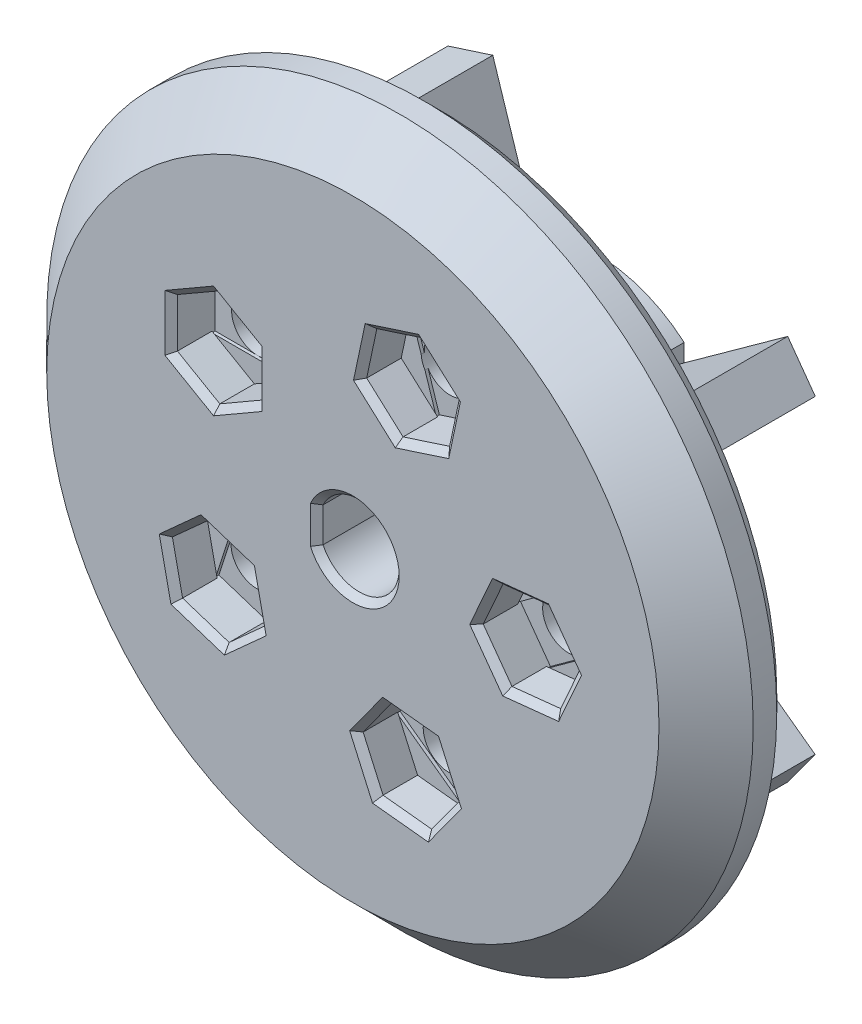
SolidWorks part; units mm, degrees
ref_plane "Front Plane" through (0, 0, 0) normal (0, 0, 1) x (1, 0, 0)
ref_plane "Top Plane" through (0, 0, 0) normal (0, 1, 0) x (1, 0, 0)
ref_plane "Right Plane" through (0, 0, 0) normal (1, 0, 0) x (0, 0, -1)
sketch "Sketch1" plane through (0, 0, 0) normal (0, 0, 1) x (1, 0, 0)
  circle A0 centre (0, 0) radius 22.5
  arc A1 (-1.7397, -1.8644) -> (-1.7397, 1.8644) centre (0, 0) ccw
  arc A2 (-1.7397, 1.8644) -> (-1.7397, -1.8644) centre (0, 0) ccw
  dimension "D1" = 45
  dimension "D2" = 5.1
extrude "Boss-Extrude1" add sketch "Sketch1" along normal blind 5.5
sketch "Sketch2" plane through (0, 0, 0) normal (0, 0, -1) x (-1, 0, 0)
  line L0 (0, 0) -> (-18.85, 0) construction
  line L1 (0, 0) -> (-5.825, 17.9274) construction
  line L2 (0, 0) -> (15.25, 11.0798) construction
  line L3 (0, 0) -> (15.25, -11.0798) construction
  line L4 (0, 0) -> (-5.825, -17.9274) construction
  line L5 (-22.5, 0) -> (-20.375, 0) construction
  circle A0 centre (-18.85, 0) radius 5.5 construction
  circle A3 centre (-18.85, 0) radius 1.525
  circle A4 centre (-5.825, 17.9274) radius 5.5 construction
  circle A5 centre (-5.825, 17.9274) radius 1.525
  circle A6 centre (15.25, 11.0798) radius 5.5 construction
  circle A7 centre (15.25, 11.0798) radius 1.525
  circle A8 centre (15.25, -11.0798) radius 5.5 construction
  circle A9 centre (15.25, -11.0798) radius 1.525
  circle A10 centre (-5.825, -17.9274) radius 5.5 construction
  circle A11 centre (-5.825, -17.9274) radius 1.525
  circle A13 centre (0, 0) radius 22.5 construction
  point P24 (0, 0)
  dimension "D1" = 11
  dimension "D2" = 3.65
  dimension "D3" = 3.05
  dimension "D4" = 5
extrude "Cut-Extrude1" cut sketch "Sketch2" against normal blind 3.5
sketch "Sketch3" plane through (0, 0, 0) normal (0, 0, -1) x (-1, 0, 0)
  line L3 (-10.9375, 0) -> (-8.55, 0) construction
  line L4 (-10.9375, 0) -> (-13.325, 0) construction
  circle A0 centre (0, 0) radius 8.55 construction
  circle A1 centre (0, 0) radius 2.55 construction
  circle A2 centre (0, 0) radius 2.55
  circle A3 centre (-18.85, 0) radius 5.525 construction
  circle A4 centre (-18.85, 0) radius 1.525 construction
  circle A6 centre (-10.9375, 0) radius 1.65
  circle A7 centre (-3.3953, 10.4497) radius 1.65
  circle A8 centre (8.8736, 6.5058) radius 1.65
  circle A9 centre (8.9141, -6.3813) radius 1.65
  circle A10 centre (-3.3299, -10.4022) radius 1.65
  point P27 (0.025, 0.0344)
  dimension "D1" = 6
  dimension "D2" = 4
  dimension "D3" = 3.3
extrude "Cut-Extrude2" cut sketch "Sketch3" against normal through all both and the other way through all
sketch "Sketch4" plane through (0, 0, 0) normal (0, 0, -1) x (-1, 0, 0)
  circle A0 centre (0, 0) radius 8.55
  circle A2 centre (0, 0) radius 2.55 construction
  circle A3 centre (0, 0) radius 2.55
  dimension "D1" = 6
extrude "Boss-Extrude2" add sketch "Sketch4" along normal blind 10
ref_plane "Plane1" through (-8.55, 0, 0) normal (-1, 0, 0) x (0, 0, 1)
sketch "Sketch8" plane through (0, 0, -10) normal (0, 0, -1) x (-1, 0, 0)
  line L0 (2.3, 1.1011) -> (2.3, -1.1011)
  line L1 (2.3, 0) -> (-2.55, 0) construction
  circle A0 centre (0, 0) radius 2.55 construction
  arc A1 (2.3, -1.1011) -> (2.3, 1.1011) centre (0, 0) ccw
  arc A2 (-2.55, 0) -> (2.3, -1.1011) centre (0, 0) ccw construction
  arc A3 (2.3, 1.1011) -> (-2.55, 0) centre (0, 0) ccw construction
  dimension "D1" = 4.85
extrude "Boss-Extrude3" add sketch "Sketch8" against normal up to surface (15.5 mm away) up to face at (1.6799, -10.4022, 5.5)
sketch "Sketch5" plane through (-8.55, 0, 0) normal (-1, 0, 0) x (0, 0, 1)
  line L0 (0, 0) -> (-10, 0) construction
  line L1 (-10, 8.55) -> (-10, -8.55) construction
  circle A0 centre (-4.2, 0) radius 1.5
  dimension "D1" = 3
  dimension "D2" = 4.2
sketch "Sketch6" plane through (0, 0, -10) normal (0, 0, -1) x (-1, 0, 0)
  line L0 (4.8, 0) -> (2.55, 0)
  line L1 (4.8, -2.8) -> (7.3, -2.8)
  line L2 (4.8, -2.8) -> (4.8, 2.8)
  line L3 (4.8, 2.8) -> (7.3, 2.8)
  line L4 (7.3, -2.8) -> (7.3, 2.8)
  circle A0 centre (0, 0) radius 2.55 construction
  dimension "D1" = 5.6
  dimension "D2" = 2.5
  dimension "D3" = 2.25
extrude "Cut-Extrude3" cut sketch "Sketch6" against normal up to surface (10 mm away) contours L1 L4 L3 L2 region at (-6.05, 0, -10) up to face at (22.5, 0, 0)
extrude "Cut-Extrude4" cut sketch "Sketch5" against normal blind 8
chamfer "Chamfer7" distance 1 angle 45 1 edges at (22.5, 0, 0)
chamfer "Chamfer8" distance 3 angle 45 1 edges at (22.5, 0, 5.5)
sketch "Sketch7" plane through (0, 0, -10) normal (0, 0, -1) x (-1, 0, 0)
  line L0 (-5.6, -6.4608) -> (-5.6, 6.4608)
  line L1 (-5.6, 0) -> (-8.55, 0) construction
  circle A0 centre (0, 0) radius 8.55 construction
  circle A1 centre (0, 0) radius 8.55 construction
  arc A2 (-5.6, 6.4608) -> (-5.6, -6.4608) centre (0, 0) ccw
  arc A3 (-5.6, -6.4608) -> (-5.6, 6.4608) centre (0, 0) ccw construction
  dimension "D1" = 2.95
extrude "Cut-Extrude5" cut sketch "Sketch7" against normal blind 2.2
sketch "Sketch9" plane through (0, 0, -10) normal (0, 0, -1) x (-1, 0, 0)
  line L0 (2, 1.5) -> (2, -1.5)
  arc A0 (2, 1.5) -> (2, -1.5) centre (0, 0) ccw
  dimension "D1" = 5
  dimension "D2" = 3
sketch "Croquis1" plane through (0, 0, 5.5) normal (0, 0, 1) x (1, 0, 0)
  line L1 (-8.8736, 3.3882) -> (-6.1736, 4.947)
  line L2 (-6.1736, 4.947) -> (-6.1736, 8.0647)
  line L3 (-6.1736, 8.0647) -> (-8.8736, 9.6235)
  line L4 (-8.8736, 9.6235) -> (-11.5736, 8.0647)
  line L5 (-11.5736, 8.0647) -> (-11.5736, 4.947)
  line L6 (-11.5736, 4.947) -> (-8.8736, 3.3882)
  circle A0 centre (-8.8736, 6.5058) radius 2.7 construction
  dimension "D1" = 5.4
extrude "Cortar-Extruir1" cut sketch "Croquis1" against normal blind 2.6
sketch "Croquis2" plane through (0, 0, 2.9) normal (0, 0, 1) x (1, 0, 0)
  line L0 (-6.1736, 4.947) -> (-6.1736, 8.0647) construction
  line L1 (-11.5736, 4.8558) -> (-6.1736, 4.8558)
  line L2 (-11.5736, 4.8558) -> (-11.5736, 8.1558)
  line L3 (-11.5736, 8.1558) -> (-6.1736, 8.1558)
  line L4 (-6.1736, 4.8558) -> (-6.1736, 8.1558)
  line L5 (-11.5736, 4.8558) -> (-6.1736, 8.1558) construction
  line L6 (-11.5736, 8.1558) -> (-6.1736, 4.8558) construction
  circle A0 centre (-8.8736, 6.5058) radius 1.65 construction
  point P0 (-8.8736, 6.5058)
extrude "Cortar-Extruir2" cut sketch "Croquis2" against normal blind 0.2
pattern_circular "MatrizC1" count 5 over 360 about axis through (0, 0, 5.5) along (0, 0, -1) of "Cortar-Extruir1", "Cortar-Extruir2" reverse direction yes
chamfer "Chaflán1" distance 0.4 angle 45 2 edges at (-2.3, 0, 5.5) (2.55, 0, 5.5)
sketch "Croquis3" plane through (0, 0, 0) normal (0, 0, -1) x (-1, 0, 0)
  line L0 (-10.9375, 0) -> (-3.3953, 10.4497) construction
  line L1 (-5.9163, 6.1725) -> (-14.3971, 12.2936)
  line L2 (1.82, 0.5887) -> (0.0643, -1.8439) construction
  line L3 (-14.3971, 12.2936) -> (-16.1529, 9.861)
  line L4 (-7.6843, 3.7488) -> (-16.1529, 9.861)
  line L5 (1.82, 0.5887) -> (-16.1529, 9.861) construction
  line L6 (-14.3971, 12.2936) -> (0.0643, -1.8439) construction
  line L7 (0.0643, -1.8439) -> (-7.6843, 3.7488) construction
  line L8 (1.82, 0.5887) -> (-5.9163, 6.1725) construction
  line L9 (4.0421, 7.5342) -> (7.2429, 17.4914)
  line L10 (7.2429, 17.4914) -> (4.3869, 18.4095)
  line L11 (1.1907, 8.4667) -> (4.3869, 18.4095)
  line L12 (8.4145, -1.5161) -> (18.8735, -1.4833)
  line L13 (18.8735, -1.4833) -> (18.8641, 1.5167)
  line L14 (8.4202, 1.4839) -> (18.8641, 1.5167)
  line L15 (1.1583, -8.4712) -> (4.4215, -18.4081)
  line L16 (4.4215, -18.4081) -> (7.2718, -17.4721)
  line L17 (4.0133, -7.5496) -> (7.2718, -17.4721)
  line L18 (-7.6986, -3.7193) -> (-16.1408, -9.8936)
  line L19 (-16.1408, -9.8936) -> (-14.3699, -12.3151)
  line L20 (-5.9399, -6.1498) -> (-14.3699, -12.3151)
  arc A0 (-5.6, 6.4608) -> (-5.6, -6.4608) centre (0, 0) ccw construction
  arc A1 (-5.9163, 6.1725) -> (-7.6843, 3.7488) centre (0, 0) ccw
  arc A2 (-5.6, 6.4608) -> (-5.9163, 6.1725) centre (0, 0) ccw construction
  arc A3 (-7.6843, 3.7488) -> (-5.6, -6.4608) centre (0, 0) ccw construction
  arc A4 (4.0421, 7.5342) -> (1.1907, 8.4667) centre (0, 0) ccw
  arc A5 (8.4145, -1.5161) -> (8.4202, 1.4839) centre (0, 0) ccw
  arc A6 (1.1583, -8.4712) -> (4.0133, -7.5496) centre (0, 0) ccw
  arc A7 (-7.6986, -3.7193) -> (-5.9399, -6.1498) centre (0, 0) ccw
  point P5 (-7.1664, 5.2249)
  point P9 (-7.1664, 5.2249)
  dimension "D1" = 10
  dimension "D2" = 3
  dimension "D3" = 5
extrude "Saliente-Extruir1" add sketch "Croquis3" along normal up to surface (7.8 mm away) up to face at (7.075, 0, -7.8)
sketch "Croquis4" plane through (0, 0, -7.8) normal (0, 0, -1) x (-1, 0, 0)
  line L3 (8.4145, -1.5161) -> (18.8735, -1.4833)
  line L4 (18.8735, -1.4833) -> (18.8641, 1.5167)
  line L5 (18.8641, 1.5167) -> (8.4202, 1.4839)
  line L6 (8.4145, -1.5161) -> (18.8735, -1.4833)
  line L7 (18.8735, -1.4833) -> (18.8641, 1.5167)
  line L8 (18.8641, 1.5167) -> (8.4202, 1.4839)
  arc A1 (8.4145, -1.5161) -> (8.4202, 1.4839) centre (0, 0) ccw
  arc A2 (8.4145, -1.5161) -> (8.4202, 1.4839) centre (0, 0) ccw
  dimension "D1" = 0
extrude "Cortar-Extruir3" cut sketch "Croquis4" against normal up to surface (7.8 mm away) up to face at (4.9799, -10.4022, 0)
sketch "Croquis5" plane through (0, 0, -10) normal (0, 0, -1) x (-1, 0, 0)
  line L0 (7.5566, 4) -> (12.5566, 4)
  line L1 (12.5566, 4) -> (12.5566, -4)
  line L2 (12.5566, -4) -> (7.5566, -4)
  arc A0 (-5.6, -6.4608) -> (-5.6, 6.4608) centre (0, 0) ccw construction
  arc A1 (4.0133, -7.5496) -> (4.0421, 7.5342) centre (0, 0) ccw construction
  arc A2 (7.5566, -4) -> (7.5566, 4) centre (0, 0) ccw
  point P5 (12.5566, 0)
  dimension "D1" = 8
  dimension "D2" = 5
extrude "Saliente-Extruir2" add sketch "Croquis5" against normal up to surface (7.8 mm away) from offset 2.2 up to face at (3.2149, -0.0004, 0) offset against normal yes
fillet "Redondeo1" radius 7 2 edges at (-7.5566, 4, -3.9) (-7.5566, -4, -3.9)
sketch "Croquis6" plane through (-7.3, 0, 0) normal (1, 0, 0) x (0, 0, -1)
  circle A0 centre (4.2, 0) radius 1.5 construction
  circle A1 centre (4.2, 0) radius 1.5
extrude "Cortar-Extruir4" cut sketch "Croquis6" against normal blind 30.2
chamfer "Chaflán2" distance 0.4 angle 45 30 edges at (8.5364, 1.0506, 5.5) (8.8186, -1.6346, 5.5) (11.2852, -2.7328, 5.5) (13.4695, -1.1457, 5.5) (13.1873, 1.5395, 5.5) (10.7207, 2.6377, 5.5) (1.6387, 8.4432, 5.5) (4.2797, 7.8819, 5.5) (6.0863, 9.8884, 5.5) (5.252, 12.4562, 5.5) (2.611, 13.0176, 5.5) (0.8043, 11.0111, 5.5) (-7.5236, 4.1676, 5.5) (-6.1736, 6.5058, 5.5) (-7.5236, 8.8441, 5.5) (-10.2236, 8.8441, 5.5) (-11.5736, 6.5058, 5.5) (-10.2236, 4.1676, 5.5) (3.6371, -7.7939, 5.5) (1.1705, -8.8921, 5.5) (0.8883, -11.5773, 5.5) (3.0726, -13.1643, 5.5) (5.5392, -12.0661, 5.5) (5.8214, -9.3809, 5.5) (-6.2885, -5.8675, 5.5) (-8.0952, -3.861, 5.5) (-10.7362, -4.4224, 5.5) (-11.5705, -6.9903, 5.5) (-9.7639, -8.9968, 5.5) (-7.1229, -8.4354, 5.5)
